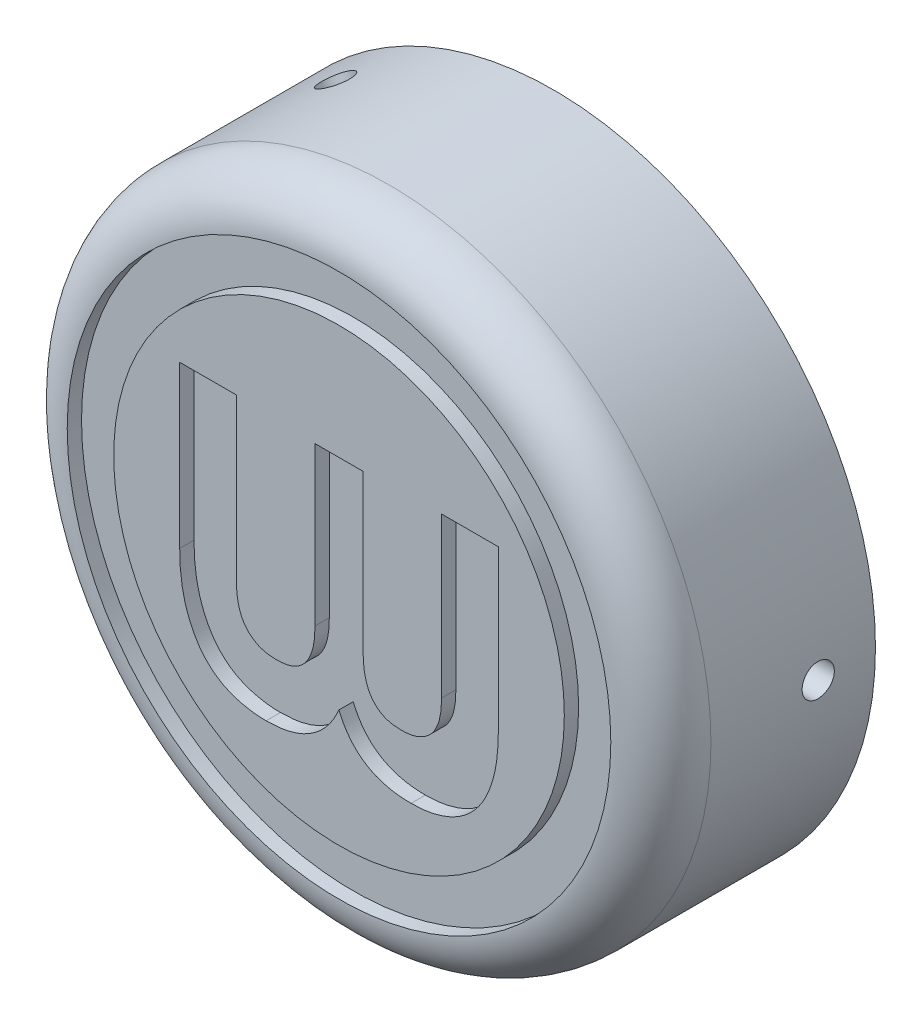
SolidWorks part; units mm, degrees
ref_plane "Plan de face" through (0, 0, 0) normal (0, 0, 1) x (1, 0, 0)
ref_plane "Plan de dessus" through (0, 0, 0) normal (0, 1, 0) x (1, 0, 0)
ref_plane "Plan de droite" through (0, 0, 0) normal (1, 0, 0) x (0, 0, -1)
sketch "Esquisse1" plane through (0, 0, 0) normal (0, 0, 1) x (1, 0, 0)
  circle A0 centre (0, 0) radius 45
  dimension "D1" = 90
extrude "Boss.-Extru.1" add sketch "Esquisse1" along normal blind 30
fillet "Congé1" radius 7 1 edges at (45, 0, 30)
sketch "Esquisse3" plane through (0, 0, 0) normal (0, 0, -1) x (-1, 0, 0)
  circle A0 centre (0, 0) radius 40
  circle A1 centre (0, 0) radius 3.15
  circle A2 centre (0, 0) radius 7
  dimension "D1" = 80
  dimension "D2" = 6.3
  dimension "D3" = 14
extrude "Enlèv. mat.-Extru.1" cut sketch "Esquisse3" against normal blind 15 contours A0 A2 | A1 region at (38.8686, 0, 0) region at (0, 0, 0)
fillet "Congé2" radius 7 1 edges at (-40, 0, 15)
sketch "Esquisse18" plane through (0, 0, 30) normal (0, 0, 1) x (1, 0, 0)
  circle A0 centre (0, 0) radius 38
  circle A1 centre (0, 0) radius 31.5
  dimension "D1" = 63
  dimension "D2" = 76
extrude "Enlèv. mat.-Extru.7" cut sketch "Esquisse18" against normal blind 2
sketch "Esquisse4" plane through (0, 0, 30) normal (0, 0, 1) x (1, 0, 0)
  line L0 (0, 0) -> (38, 0) construction
  line L1 (38, 0) -> (0, -38) construction
  line L2 (0, -38) -> (0, 38) construction
  line L3 (38, 0) -> (38, -35) construction
  line L4 (38, -35) -> (38, 35) construction
  line L5 (24.7487, 28.8358) -> (24.7487, -28.8358) construction
  line L6 (24.7487, -28.8358) -> (-24.7487, -28.8358) construction
  line L7 (-24.7487, -28.8358) -> (-24.7487, 28.8358) construction
  line L8 (-24.7487, 28.8358) -> (24.7487, 28.8358) construction
  line L9 (22.2739, -22.2739) -> (-22.2739, 22.2739) construction
  line L10 (-22.2739, 22.2739) -> (-22.2739, -22.2739) construction
  line L11 (-22.2739, -22.2739) -> (22.2739, -22.2739) construction
  line L12 (22.2739, -22.2739) -> (22.2739, 22.2739) construction
  line L13 (22.2739, 22.2739) -> (-22.2739, 22.2739) construction
  line L14 (-22.2739, 22.2739) -> (-22.2739, -26.7261) construction
  circle A0 centre (0, 0) radius 38 construction
  circle A1 centre (0, 0) radius 31.5 construction
  text T0 "E" font "Nasalization Rg" height 44.55
  dimension "D3" = 45
  dimension "D1" = 49.4974
  dimension "D2" = 57.6715
  dimension "D4" = 90
  dimension "D5" = 45
  dimension "D6" = 44.5477
  dimension "D7" = 45
  dimension "D8" = 49
extrude "Enlèv. mat.-Extru.2" cut sketch "Esquisse4" against normal blind 2
sketch "Esquisse12" plane through (0, 0, 0) normal (0, 0, -1) x (-1, 0, 0)
  line L1 (0, -7) -> (-14, -7)
  line L2 (0, -7) -> (0, 7)
  line L3 (0, 7) -> (-14, 7)
  line L4 (-14, -7) -> (-14, 7)
  circle A0 centre (0, 0) radius 7 construction
  circle A1 centre (0, 0) radius 7 construction
  circle A2 centre (0, 0) radius 3.15
  circle M1 centre (0, 0) radius 3.15
  circle M2 centre (0, 0) radius 7
  dimension "D1" = 14
  dimension "D2" = 14
  dimension "D3" = 7
extrude "Boss.-Extru.3" add sketch "Esquisse12" against normal blind 22 contours L2 M2 M1 | L4 L1 L3 M2 region at (3.3858, 0, 0) region at (9.6053, 0, 0)
sketch "Esquisse13" plane through (14, 0, 0) normal (1, 0, 0) x (0, 0, -1)
  line L0 (-15, 7) -> (0, 7) construction
  line L1 (-10.1651, 3.75) -> (-12.3301, 0)
  line L2 (-12.3301, 0) -> (-10.1651, -3.75)
  line L3 (-10.1651, -3.75) -> (-5.8349, -3.75)
  line L4 (-5.8349, -3.75) -> (-3.6699, 0)
  line L5 (-3.6699, 0) -> (-5.8349, 3.75)
  line L6 (-5.8349, 3.75) -> (-10.1651, 3.75)
  line L7 (0, -7) -> (0, 7) construction
  circle A0 centre (-8, 0) radius 3.75 construction
  dimension "D1" = 7.5
  dimension "D2" = 0
  dimension "D3" = 8
  dimension "D4" = 7
extrude "Enlèv. mat.-Extru.3" cut sketch "Esquisse13" against normal blind 8
sketch "Esquisse14" plane through (0, 0, 0) normal (0, 0, -1) x (-1, 0, 0)
  line L0 (-14, -7) -> (-14, 7) construction
  line L1 (-14, 3.75) -> (-6, 3.75)
  line L2 (-14, 3.75) -> (-14, -3.75)
  line L3 (-14, -3.75) -> (-6, -3.75)
  line L4 (-6, 3.75) -> (-6, -3.75)
  line L5 (0, 7) -> (-14, 7) construction
  point P6 (-6, 0)
  dimension "D1" = 7.5
  dimension "D2" = 7
  dimension "D3" = 8
extrude "Enlèv. mat.-Extru.4" cut sketch "Esquisse14" against normal blind 8
sketch "Esquisse15" plane through (0, 0, 15) normal (0, 0, -1) x (-1, 0, 0)
  line L1 (-14, 7) -> (-15.5, 7)
  line L2 (-14, 7) -> (-14, -7)
  line L3 (-14, -7) -> (-15.5, -7)
  line L4 (-15.5, 7) -> (-15.5, -7)
  line L5 (-14, 7) -> (-11.5, 7)
  line L6 (-14, 7) -> (-14, -7)
  line L7 (-14, -7) -> (-11.5, -7)
  line L8 (-11.5, 7) -> (-11.5, -7)
  line M8 (0, -7) -> (-14, -7)
  line M9 (-14, -7) -> (-14, 7)
  line M10 (-14, 7) -> (0, 7)
  dimension "D1" = 14
  dimension "D2" = 4
  dimension "D3" = 5.5
extrude "Boss.-Extru.4" add sketch "Esquisse15" along normal blind 15 contours L1 L4 L3 M9 | L8 M10 M9 M8 region at (14.75, 0, 15) region at (12.75, 0, 15)
sketch "Esquisse16" plane through (15.5, 0, 0) normal (1, 0, 0) x (0, 0, -1)
  line L0 (0, 7) -> (-15, 7) construction
  line L2 (0, 7) -> (0, -7) construction
  circle A0 centre (-8, 0) radius 2.25
  dimension "D3" = 4.5
  dimension "D1" = 7
  dimension "D2" = 8
extrude "Enlèv. mat.-Extru.5" cut sketch "Esquisse16" against normal blind 15 and the other way blind 31
sketch "Esquisse17" plane through (15.5, 0, 0) normal (1, 0, 0) x (0, 0, -1)
  circle A0 centre (-8.3177, 0) radius 7
extrude "Enlèv. mat.-Extru.6" cut sketch "Esquisse17" along normal blind 8
pattern_circular "Répétition circulaire1" count 3 every 120 about axis through (0, 0, 0) along (0, 0, -1) of "Boss.-Extru.3", "Enlèv. mat.-Extru.3", "Enlèv. mat.-Extru.4", "Boss.-Extru.4", "Enlèv. mat.-Extru.5", "Enlèv. mat.-Extru.6"
